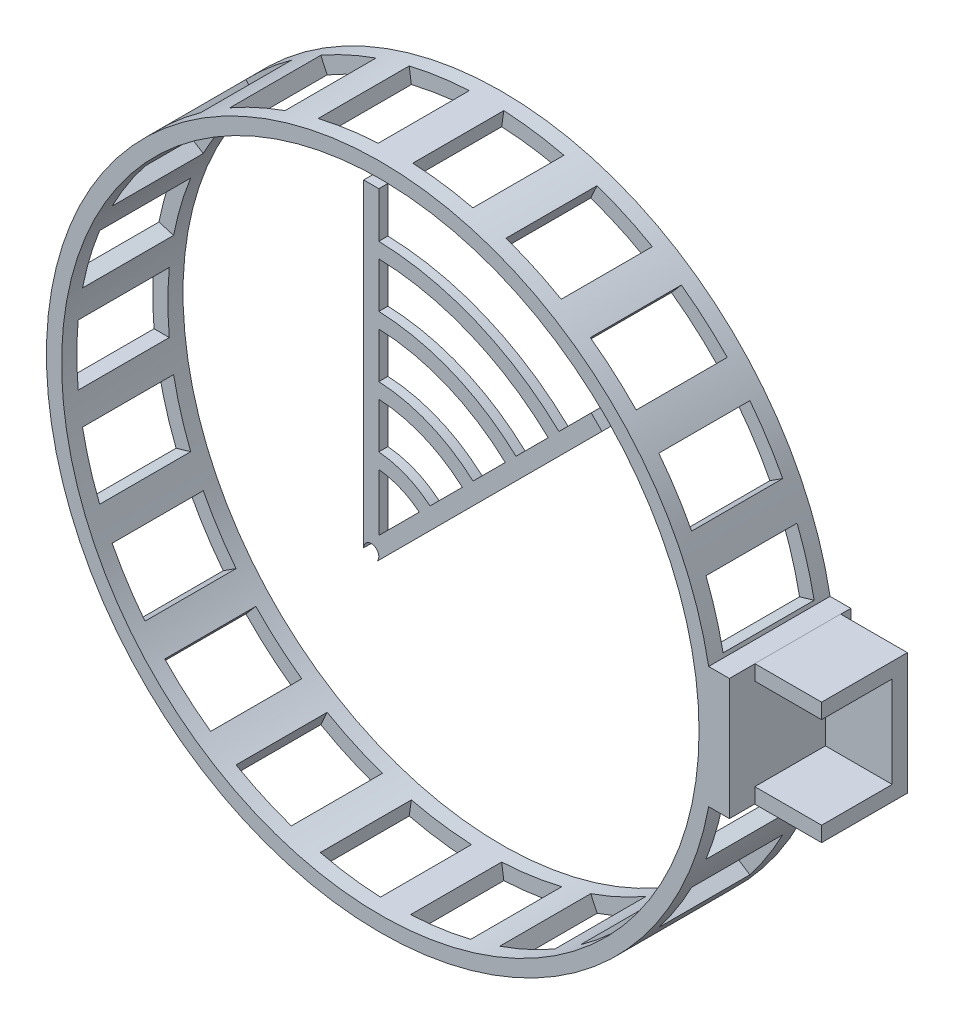
SolidWorks part; units mm, degrees
ref_plane "Plan de face" through (0, 0, 0) normal (0, 0, 1) x (1, 0, 0)
ref_plane "Plan de dessus" through (0, 0, 0) normal (0, 1, 0) x (1, 0, 0)
ref_plane "Plan de droite" through (0, 0, 0) normal (1, 0, 0) x (0, 0, -1)
sketch "Esquisse1" plane through (0, 0, 0) normal (0, 0, 1) x (1, 0, 0)
  circle A0 centre (0, 0) radius 105
  circle A1 centre (0, 0) radius 110
  dimension "D1" = 210
  dimension "D2" = 220
extrude "Boss.-Extru.1" add sketch "Esquisse1" along normal blind 40
ref_plane "Plan1" through (110, 0, 0) normal (1, 0, 0) x (0, 0, -1)
sketch "Esquisse3" plane through (110, 0, 0) normal (1, 0, 0) x (0, 0, -1)
  line L0 (0, 0) -> (-40, 0) construction
  line L1 (-40, 110) -> (-40, -110) construction
  line L2 (-20, 110) -> (-20, -110) construction
  line L3 (0, 110) -> (-40, 110) construction
  line L4 (-40, -110) -> (0, -110) construction
  line L6 (-5, 10) -> (-35, 10)
  line L7 (-5, 10) -> (-5, -10)
  line L8 (-5, -10) -> (-35, -10)
  line L9 (-35, 10) -> (-35, -10)
  line L10 (-5, 10) -> (-35, -10) construction
  line L11 (-5, -10) -> (-35, 10) construction
  point P11 (-20, 0)
  dimension "D1" = 30
  dimension "D2" = 20
extrude "Enlèv. mat.-Extru.1" cut sketch "Esquisse3" against normal through all
ref_axis "Axe1" through (0, 0, -2) along (0, 0, 1)
pattern_circular "Répétition circulaire1" count 22 over 360 about axis through (0, 0, -2) along (0, 0, 1) of "Enlèv. mat.-Extru.1"
ref_plane "Plan2" through (130, 0, 0) normal (1, 0, 0) x (0, 0, -1)
ref_plane "Plan4" through (115, 0, 0) normal (1, 0, 0) x (0, 0, -1)
sketch "Esquisse9" plane through (115, 0, 0) normal (1, 0, 0) x (0, 0, -1)
  line L0 (0, 0) -> (-40, 0) construction
  line L5 (-40, 110) -> (-40, -110) construction
  line L7 (-40, 20) -> (0, 20)
  line L8 (-40, 20) -> (-40, -20)
  line L9 (-40, -20) -> (0, -20)
  line L10 (0, 20) -> (0, -20)
  line L11 (-40, 20) -> (0, -20) construction
  line L12 (-40, -20) -> (0, 20) construction
  point P4 (-20, 0)
  dimension "D1" = 40
  dimension "D2" = 40
extrude "Boss.-Extru.4" add sketch "Esquisse9" against normal up to surface (6.8335 mm away) up to face at (-105.3257, -30.9264, 20)
sketch "Esquisse24" plane through (115, 0, 115) normal (-1, 0, 0) x (0, 0, 1)
  line L0 (-75, -20) -> (-115, -20) construction
  line L23 (-95, 0) -> (-95, -15.05) construction
  line L67 (-83.37, -15.05) -> (-106.63, -15.05)
  line L68 (-106.63, -15.05) -> (-106.63, 15.05)
  line L77 (-106.63, 15.05) -> (-83.37, 15.05)
  line L78 (-83.37, -20.05) -> (-111.63, -20.05)
  line L123 (-111.63, -20.05) -> (-111.63, 20.05)
  line L124 (-75, 0) -> (-115, 0) construction
  line L125 (-111.63, 20.05) -> (-83.37, 20.05)
  line L126 (-83.37, -20.05) -> (-83.37, -15.05)
  line L127 (-115, -20) -> (-115, 20) construction
  line L128 (-95, 0) -> (-95, 6.1628) construction
  line L153 (-83.37, 15.05) -> (-83.37, 20.05)
  point P18 (-95, -15.05)
  dimension "D1" = 11.63
  dimension "D2" = 15.05
  dimension "D3" = 23.26
  dimension "D5" = 5
  dimension "D6" = 20
  dimension "D7" = 20
  dimension "D4" = 30.1
extrude "Boss.-Extru.22" add sketch "Esquisse24" against normal blind 22
sketch "Esquisse14" plane through (110, 0, 0) normal (1, 0, 0) x (0, 0, -1)
  line L4 (-35, -10) -> (-5, -10)
  line L5 (-35, 10) -> (-35, -10)
  line L6 (-5, 10) -> (-35, 10)
  line L7 (-5, -10) -> (-5, 10)
  line L8 (-35, -10) -> (-5, -10)
  line L9 (-35, 10) -> (-35, -10)
  line L10 (-5, 10) -> (-35, 10)
  line L11 (-5, -10) -> (-5, 10)
  dimension "D1" = 0
extrude "Boss.-Extru.9" add sketch "Esquisse14" against normal up to surface (5.4773 mm away) up to face at (-100.5178, -29.5147, 20)
sketch "Esquisse15" plane through (0, 0, 40) normal (0, 0, 1) x (1, 0, 0)
  line L0 (0, 3.5355) -> (0, 0) construction
  line L1 (-2.5, 0) -> (2.5, 0) construction
  line L6 (1.7678, -1.7678) -> (75.9929, 72.4574)
  line L7 (2.5, 24.8747) -> (2.5, 6.0355)
  line L8 (19.3717, 22.9072) -> (30.0029, 33.5384)
  line L14 (2.5, 104.9702) -> (2.5, 89.9653)
  line L15 (-2.5, 104.9702) -> (-2.5, 0)
  line L16 (33.5434, 37.0789) -> (44.1602, 47.6957)
  line L17 (2.5, 44.9305) -> (2.5, 29.8957)
  line L18 (47.6981, 51.2337) -> (58.3103, 61.8458)
  line L19 (2.5, 64.9519) -> (2.5, 49.9375)
  line L20 (61.8473, 65.3828) -> (72.4574, 75.9929)
  line L21 (2.5, 84.9632) -> (2.5, 69.9553)
  line L22 (2.5, 6.0355) -> (15.8213, 19.3568)
  arc A0 (2.5, 89.9653) -> (61.8473, 65.3828) centre (0, 0) cw
  circle A1 centre (0, 0) radius 2.5
  arc A2 (2.5, 84.9632) -> (58.3103, 61.8458) centre (0, 0) cw
  arc A3 (2.5, 69.9553) -> (47.6981, 51.2337) centre (0, 0) cw
  arc A5 (2.5, 64.9519) -> (44.1602, 47.6957) centre (0, 0) cw
  arc A6 (2.5, 49.9375) -> (33.5434, 37.0789) centre (0, 0) cw
  arc A7 (2.5, 44.9305) -> (30.0029, 33.5384) centre (0, 0) cw
  arc A8 (2.5, 29.8957) -> (19.3717, 22.9072) centre (0, 0) cw
  arc A9 (2.5, 24.8747) -> (15.8213, 19.3568) centre (0, 0) cw
  circle A12 centre (0, 0) radius 105 construction
  arc A13 (75.9929, 72.4574) -> (72.4574, 75.9929) centre (0, 0) ccw
  arc A14 (2.5, 104.9702) -> (-2.5, 104.9702) centre (0, 0) ccw
  point P48 (0, 0)
  circle M16 centre (0, 0) radius 105
  dimension "D4" = 65
  dimension "D5" = 50
  dimension "D6" = 45
  dimension "D7" = 30
  dimension "D8" = 25
  dimension "D1" = 90
  dimension "D3" = 70
  dimension "D2" = 85
extrude "Boss.-Extru.13" add sketch "Esquisse15" along normal blind 3 contours A1 L6 L20 A0 L14 L15 A8 L17 A7 L8 A6 L19 A5 L16 A3 L21 A2 L18 L7 A9 L22 M16 region at (2.4321, -1.0074, 40)
